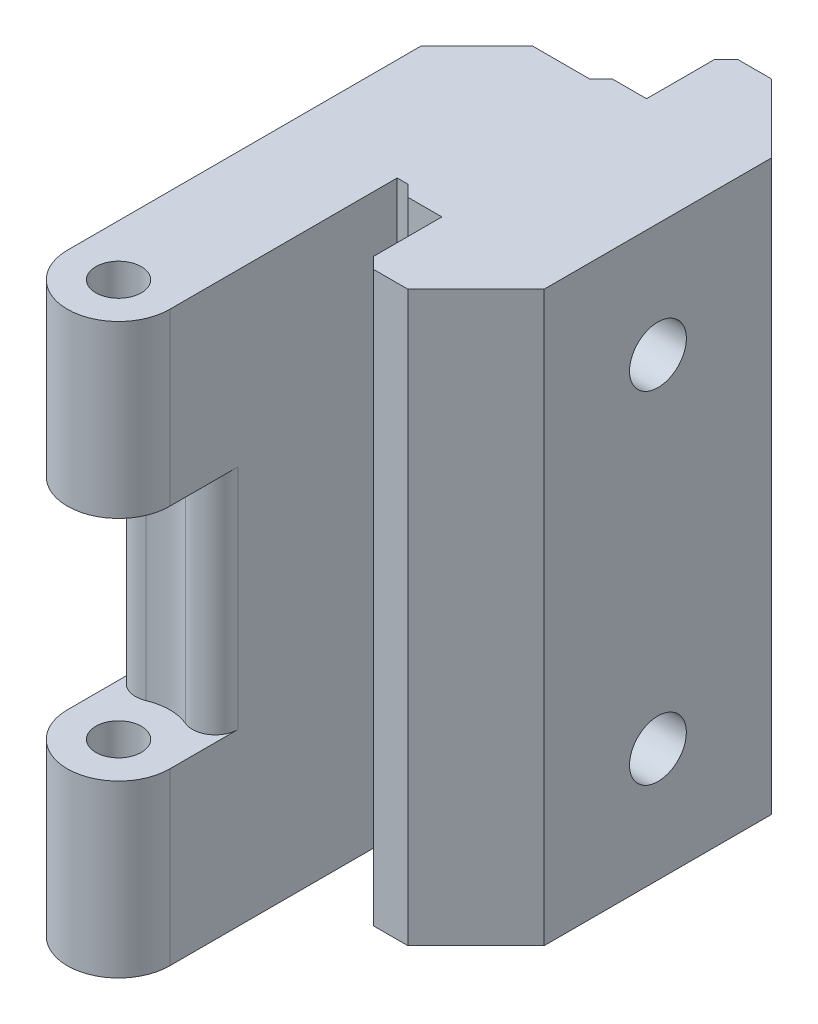
SolidWorks part; units mm, degrees
ref_plane "Front Plane" through (0, 0, 0) normal (0, 0, 1) x (1, 0, 0)
ref_plane "Top Plane" through (0, 0, 0) normal (0, 1, 0) x (1, 0, 0)
ref_plane "Right Plane" through (0, 0, 0) normal (1, 0, 0) x (0, 0, -1)
sketch "Sketch1" plane through (0, 0, 0) normal (0, 1, 0) x (1, 0, 0)
  line L0 (2, -3.5) -> (2, 0)
  line L1 (0, 0) -> (2, 0)
  line L2 (0, 0) -> (0, 9)
  line L3 (0, 9) -> (2, 9)
  line L5 (2, 12.5) -> (4, 12.5)
  line L6 (2, 12.5) -> (4, 12.5)
  line L7 (2, 12.5) -> (2, 9)
  line L8 (2, -3.5) -> (4, -3.5)
  line L9 (7, 9.5) -> (7, -0.5)
  line L10 (4, 12.5) -> (7, 9.5)
  line L11 (4, -3.5) -> (7, -0.5)
  line L12 (2, 9) -> (2, 12.5)
  line L13 (2, 0) -> (2, -3.5)
  point P8 (2, 4.5)
  dimension "D1" = 2
  dimension "D2" = 9
extrude "Boss-Extrude1" add sketch "Sketch1" along normal blind 25 contours L8 L11 L9 L10 L5 L7 L3 L2 L1 L0 region at (3.6404, 0, -4.5)
sketch "Sketch2" plane through (0, 0, 0) normal (-1, 0, 0) x (0, 0, 1)
  circle A0 centre (-4.5, 20) radius 1.25
  circle A1 centre (-4.5, 5) radius 1.25
  point P9 (-4.5, 12.5)
  point P12 (-4.5, 12.5)
extrude "Cut-Extrude1" cut sketch "Sketch2" against normal blind 25
chamfer "Chamfer1" distance 0.5 angle 45 2 edges at (2, 12.5, 3.5) (2, 12.5, -12.5)
chamfer "Chamfer2" distance 0.5 angle 45 2 edges at (0, 12.5, 0) (0, 12.5, -9)
sketch "Sketch5" plane through (0, 0, 0) normal (0, -1, 0) x (1, 0, 0)
  line L1 (0, -8.5) -> (-4.9648, -8.5)
  line L2 (0, -8.5) -> (0, -0.5)
  line L3 (0, -0.5) -> (-0.4648, -0.5)
  line L4 (-4.9648, -8.5) -> (-4.9648, -0.5)
  line L6 (-4.9648, -0.5) -> (-4.9648, 9.5)
  line L8 (-0.4648, -0.5) -> (-0.4648, 9.5)
  arc A0 (-0.4648, 9.5) -> (-4.9648, 9.5) centre (-2.7148, 9.5) ccw
  circle A1 centre (-2.7148, 9.5) radius 1
extrude "Boss-Extrude2" add sketch "Sketch5" against normal blind 25
chamfer "Chamfer3" distance 2.45 angle 45 1 edges at (-4.9648, 12.5, -8.5)
ref_plane "Plane1" through (0, 12.5, 0) normal (0, -1, 0) x (-1, 0, 0)
sketch "Sketch6" plane through (0, 12.5, 0) normal (0, -1, 0) x (-1, 0, 0)
  circle A0 centre (2.7148, -9.5) radius 2.25
extrude "Cut-Extrude3" cut sketch "Sketch6" against normal mid plane 10
fillet "Fillet1" radius 1 2 edges at (-4.9648, 12.5, 9.5) (-0.4648, 12.5, 9.5)
